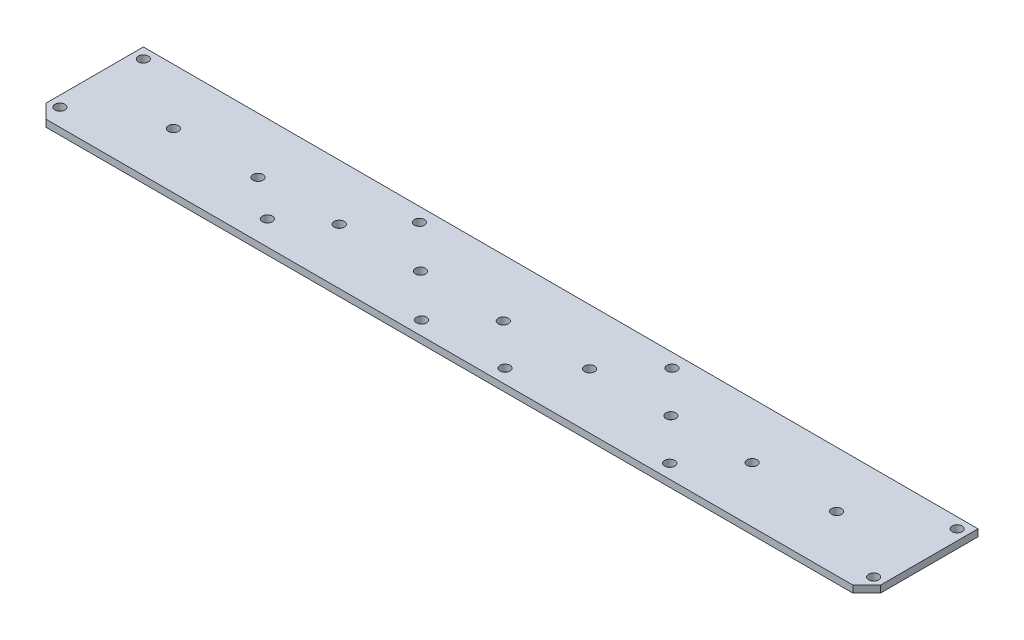
SolidWorks part; units mm, degrees
ref_plane "Front Plane" through (0, 0, 0) normal (0, 0, 1) x (1, 0, 0)
ref_plane "Top Plane" through (0, 0, 0) normal (0, 1, 0) x (1, 0, 0)
ref_plane "Right Plane" through (0, 0, 0) normal (1, 0, 0) x (0, 0, -1)
sketch "Sketch2" plane through (0, 0, 0) normal (0, 1, 0) x (1, 0, 0)
  line L0 (0, 0) -> (0, 50.8)
  line L1 (0, 50.8) -> (381, 50.8)
  line L2 (381, 50.8) -> (381, 0)
  line L3 (381, 0) -> (0, 0)
  dimension "D1" = 50.8
  dimension "D2" = 381
extrude "Boss-Extrude1" add sketch "Sketch2" along normal blind 3.175
sketch "Sketch3" plane through (0, 0, 0) normal (0, 1, 0) x (1, 0, 0)
  line L0 (0, 6.35) -> (6.35, 0) construction
  line L1 (374.65, 0) -> (381, 6.35) construction
  line L2 (0, 6.35) -> (6.35, 0)
  line L3 (374.65, 0) -> (381, 6.35)
  line L4 (0, 6.35) -> (0, 0)
  line L5 (0, 0) -> (6.35, 0)
  line L7 (381, 6.35) -> (381, 0)
  line L8 (381, 0) -> (374.65, 0)
  circle A19 centre (96.266, 11.1125) radius 2.286 construction
  circle A20 centre (284.734, 6.35) radius 2.286 construction
  circle A22 centre (132.334, 44.45) radius 2.286 construction
  circle A23 centre (247.65, 44.45) radius 2.286 construction
  circle A24 centre (209.55, 6.35) radius 2.286 construction
  circle A25 centre (171.45, 6.35) radius 2.286 construction
  circle A26 centre (4.7625, 7.9375) radius 2.286 construction
  circle A27 centre (4.7625, 46.0375) radius 2.286 construction
  circle A28 centre (39.116, 25.4) radius 2.286 construction
  circle A29 centre (77.724, 25.4) radius 2.286 construction
  circle A30 centre (114.808, 25.4) radius 2.286 construction
  circle A32 centre (190.5, 24.6062) radius 2.286 construction
  circle A36 centre (341.884, 25.4) radius 2.286 construction
  circle A37 centre (376.2375, 7.9375) radius 2.286 construction
  circle A38 centre (376.2375, 46.0375) radius 2.286 construction
  circle A39 centre (96.266, 11.1125) radius 2.286
  circle A40 centre (284.734, 6.35) radius 2.286
  circle A42 centre (132.334, 44.45) radius 2.286
  circle A43 centre (247.65, 44.45) radius 2.286
  circle A44 centre (209.55, 6.35) radius 2.286
  circle A45 centre (171.45, 6.35) radius 2.286
  circle A46 centre (4.7625, 7.9375) radius 2.286
  circle A47 centre (4.7625, 46.0375) radius 2.286
  circle A48 centre (39.116, 25.4) radius 2.286
  circle A49 centre (77.724, 25.4) radius 2.286
  circle A50 centre (114.808, 25.4) radius 2.286
  circle A52 centre (190.5, 24.6062) radius 2.286
  circle A56 centre (341.884, 25.4) radius 2.286
  circle A57 centre (376.2375, 7.9375) radius 2.286
  circle A58 centre (376.2375, 46.0375) radius 2.286
  circle A59 centre (303.276, 25.4) radius 2.286
  circle A60 centre (266.192, 25.4) radius 2.286
  circle A61 centre (229.108, 25.4) radius 2.286
  circle A62 centre (151.892, 25.4) radius 2.286
  dimension "D1" = 4.572
extrude "Cut-Extrude1" cut sketch "Sketch3" along normal through all
